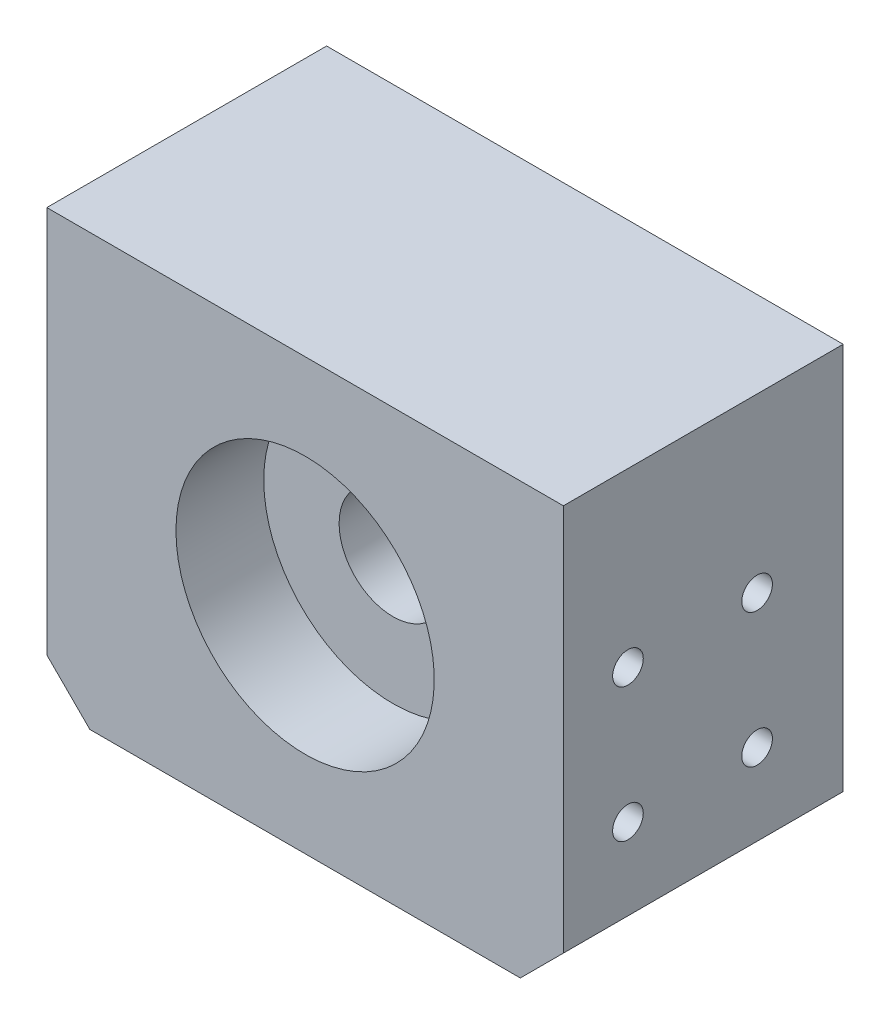
SolidWorks part; units mm, degrees
material "1060 Alloy"
ref_plane "Front" through (0, 0, 0) normal (0, 0, 1) x (1, 0, 0)
ref_plane "Top" through (0, 0, 0) normal (0, 1, 0) x (1, 0, 0)
ref_plane "Right" through (0, 0, 0) normal (1, 0, 0) x (0, 0, -1)
sketch "Sketch1" plane through (0, 0, 0) normal (0, 0, 1) x (1, 0, 0)
  line L1 (19.05, -15.875) -> (-19.05, -15.875)
  line L2 (19.05, -15.875) -> (19.05, 15.875)
  line L3 (19.05, 15.875) -> (-19.05, 15.875)
  line L4 (-19.05, -15.875) -> (-19.05, 15.875)
  line L5 (19.05, -15.875) -> (-19.05, 15.875) construction
  line L6 (19.05, 15.875) -> (-19.05, -15.875) construction
  point P0 (0, 0)
  dimension "D1" = 31.75
  dimension "D2" = 38.1
extrude "Boss-Extrude1" add sketch "Sketch1" along normal blind 20.6375
sketch "Sketch2" plane through (0, 0, 0) normal (0, 0, -1) x (-1, 0, 0)
  circle A0 centre (0, 0) radius 11.1125
  dimension "D1" = 22.225
extrude "Cut-Extrude1" cut sketch "Sketch2" against normal blind 6.985
sketch "Sketch3" plane through (0, 0, 6.985) normal (0, 0, -1) x (-1, 0, 0)
  circle A0 centre (0, 0) radius 8.255
  dimension "D1" = 16.51
extrude "Cut-Extrude2" cut sketch "Sketch3" against normal blind 2.413
sketch "Sketch4" plane through (0, 0, 9.398) normal (0, 0, -1) x (-1, 0, 0)
  circle A0 centre (0, 0) radius 3.9688
  dimension "D1" = 7.9375
extrude "Cut-Extrude3" cut sketch "Sketch4" against normal through all
sketch "Sketch6" plane through (0, 0, 9.398) normal (0, 0, -1) x (-1, 0, 0)
  circle A0 centre (0, 0) radius 9.525
  dimension "D1" = 19.05
extrude "Cut-Extrude4" cut sketch "Sketch6" against normal through all from offset 4.7625 offset against normal yes
chamfer "Chamfer1" distance 3.175 angle 45 2 edges at (19.05, -15.875, 10.3187) (-19.05, -15.875, 10.3187)
hole_wizard "#4-40 Tapped Hole2" positions "Sketch7" profile "Sketch8" tap size "#4-40" standard "ANSI Inch"
sketch "Sketch7" plane through (-19.05, -28.277, 98.8948) normal (-1, 0, 0) x (0, 0, 1)
  point P0 (-92.5448, 31.452)
  point P1 (-83.0198, 31.452)
  point P2 (-83.0198, 21.927)
  point P3 (-92.5448, 21.927)
sketch "Sketch8" plane through (-19.05, 3.175, 6.35) normal (0, 1, 0) x (0, 0, 1)
  line L0 (0, 0) -> (0, 8.2992)
  line L1 (0, 8.2992) -> (1.1303, 7.62)
  line L2 (1.1303, 7.62) -> (1.1303, 0)
  line L5 (1.1303, 0) -> (0, 0)
  line L10 (0, 8.2992) -> (-1.1303, 7.62) construction
  line L11 (0, -6.35) -> (0, 107.95) construction
  dimension "Tap Drill Dia." = 2.2606
  dimension "Tap Drill Depth" = 7.62
  dimension "Drill Angle" = 118
cosmetic thread "Hole Thread5" parameters "D1"=5.588, "D2"=2.8448
cosmetic thread "Hole Thread6" parameters "D1"=5.588, "D2"=2.8448
cosmetic thread "Hole Thread7" parameters "D1"=5.588, "D2"=2.8448
cosmetic thread "Hole Thread8" parameters "D1"=5.588, "D2"=2.8448
hole_wizard "#4-40 Tapped Hole1" positions "Sketch11" profile "Sketch12" tap size "#4-40" standard "ANSI Inch"
sketch "Sketch11" plane through (19.05, -28.277, 98.8948) normal (1, 0, 0) x (0, 0, -1)
  point P0 (92.5448, 31.452)
  point P1 (83.0198, 31.452)
  point P2 (83.0198, 21.5728)
  point P3 (92.5448, 21.5728)
  point P8 (0, 0)
  point P9 (0, 0)
  point P10 (0, 0)
  point P11 (0, 0)
  point P12 (0, 0)
  point P13 (0, 0)
  point P14 (79.0018, 31.452)
sketch "Sketch12" plane through (19.05, 3.175, 6.35) normal (0, 1, 0) x (0, 0, -1)
  line L0 (0, 0) -> (0, 8.2992)
  line L1 (0, 8.2992) -> (1.1303, 7.62)
  line L2 (1.1303, 7.62) -> (1.1303, 0)
  line L5 (1.1303, 0) -> (0, 0)
  line L10 (0, 8.2992) -> (-1.1303, 7.62) construction
  line L11 (0, -6.35) -> (0, 107.95) construction
  dimension "Tap Drill Dia." = 2.2606
  dimension "Tap Drill Depth" = 7.62
  dimension "Drill Angle" = 118
cosmetic thread "Hole Thread1" parameters "D1"=5.588, "D2"=2.8448
cosmetic thread "Hole Thread2" parameters "D1"=5.588, "D2"=2.8448
cosmetic thread "Hole Thread3" parameters "D1"=5.588, "D2"=2.8448
cosmetic thread "Hole Thread4" parameters "D1"=5.588, "D2"=2.8448
